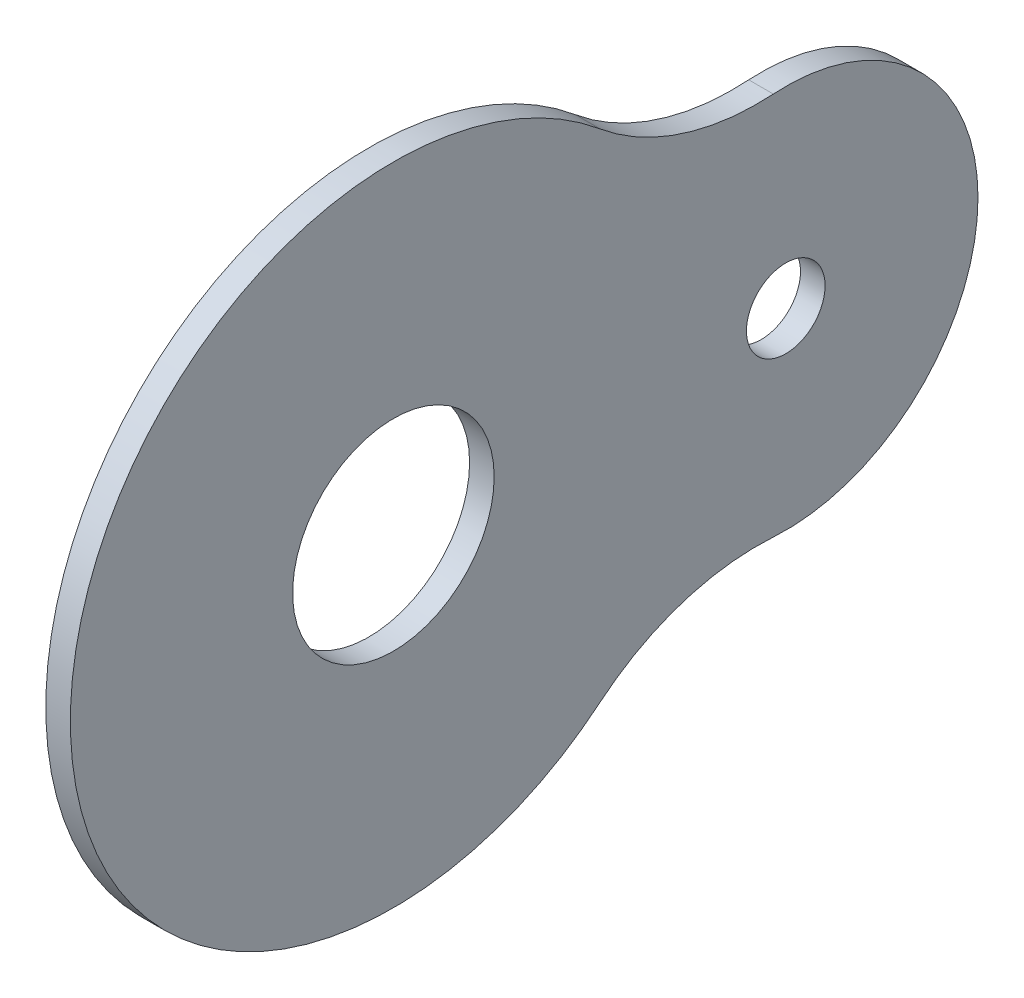
SolidWorks part; units mm, degrees
material "ABS"
ref_plane "Спереди" through (0, 0, 0) normal (0, 0, 1) x (1, 0, 0)
ref_plane "Сверху" through (0, 0, 0) normal (0, 1, 0) x (1, 0, 0)
ref_plane "Справа" through (0, 0, 0) normal (1, 0, 0) x (0, 0, -1)
sketch "Эскиз1" plane through (0, 0, 0) normal (1, 0, 0) x (0, 0, -1)
  circle A0 centre (27.5751, 7.5072) radius 1.5
  circle A1 centre (27.5751, 7.5072) radius 18.465
  circle A2 centre (14.9975, 25.9822) radius 7.885
  circle A3 centre (14.9975, 25.9822) radius 1.5
  circle A4 centre (0, 0) radius 13.14
  circle A5 centre (15.96, 0) radius 7.82
  circle A6 centre (0, 0) radius 4.1
  circle A7 centre (15.96, 0) radius 1.6
  point P6 (15.96, 0)
  point P7 (0, 0)
  dimension "D1" = 3
  dimension "D2" = 36.93
  dimension "D3" = 15.77
  dimension "D5" = 3
  dimension "D10" = 26.28
  dimension "D11" = 15.64
  dimension "D12" = 8.2
  dimension "D13" = 3.2
  dimension "D4" = 22.35
  dimension "D6" = 15.96
  dimension "D7" = 30
  dimension "D8" = 26
  dimension "D9" = 13.83
extrude "Бобышка-Вытянуть1" add sketch "Эскиз1" along normal blind 1 contours A5 A1 A4 | A1 A5 A4 | A4 A5 A1 | A5 A4 A1 | A1 A5 A4 A7 | A4 A5 A1 region at (0, -6.2019, -13.7944) region at (0, 0.4874, -17.9076) region at (0, -1.7073, -10.1004) region at (0, 1.9218, -11.5291) region at (0, -1.8181, 12.6499) region at (0, 6.8202, -9.9491)
fillet "Скругление1" radius 10 2 edges at (0.5, -6.4049, -11.4733) (0.5, 6.4049, -11.4733)
